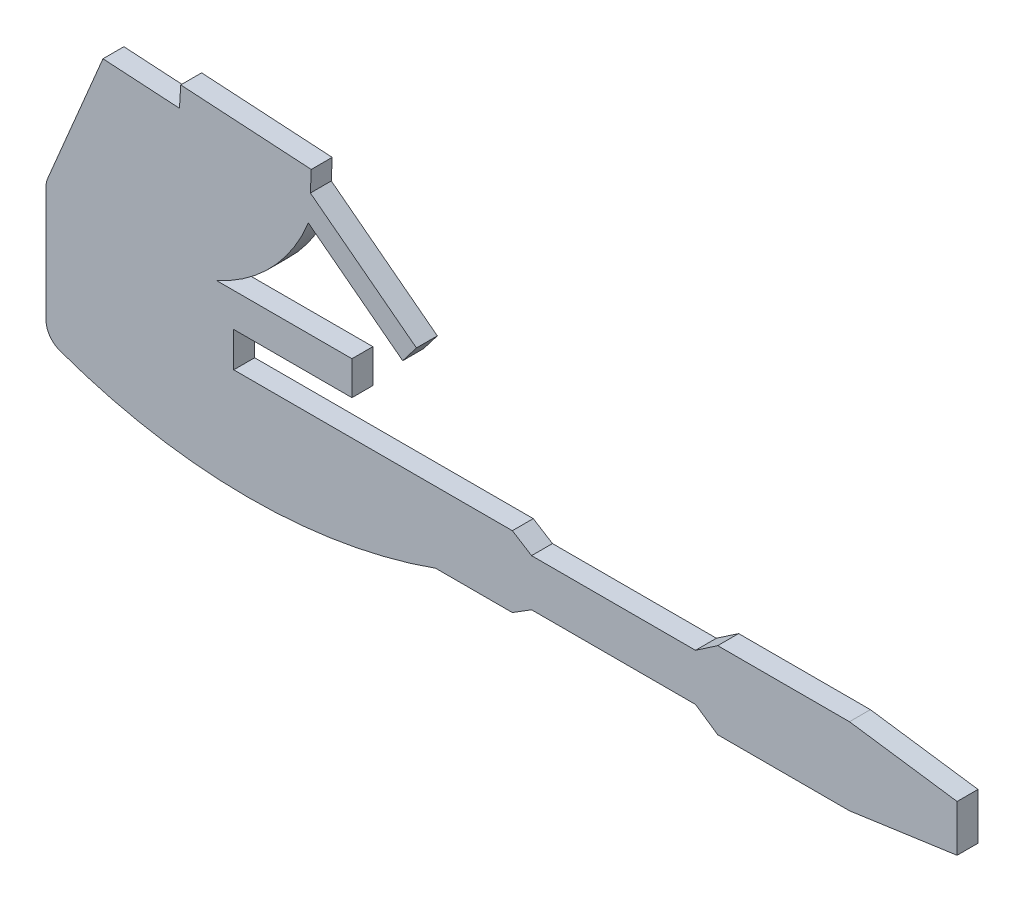
SolidWorks part; units mm, degrees
ref_plane "Front Plane" through (0, 0, 0) normal (0, 0, 1) x (1, 0, 0)
ref_plane "Top Plane" through (0, 0, 0) normal (0, 1, 0) x (1, 0, 0)
ref_plane "Right Plane" through (0, 0, 0) normal (1, 0, 0) x (0, 0, -1)
sketch "Sketch1" plane through (0, 0, 0) normal (0, 0, 1) x (1, 0, 0)
  line L0 (-76.7542, -61.1742) -> (-76.6619, -59.653)
  line L1 (-76.6619, -59.653) -> (-67.1495, -60.2304)
  line L2 (-67.1495, -60.2304) -> (-67.2138, -61.7533)
  line L3 (-67.2138, -61.7533) -> (-59.4864, -67.6638)
  line L4 (-59.4864, -67.6638) -> (-60.4861, -68.9708)
  line L5 (-60.4861, -68.9708) -> (-67.3609, -63.7124)
  line L6 (-74.0519, -70.6934) -> (-64.1851, -70.6934)
  line L7 (-64.1851, -70.6934) -> (-64.1851, -73.153)
  line L8 (-64.1851, -73.153) -> (-72.7983, -73.153)
  line L9 (-72.7983, -73.153) -> (-72.7983, -75.7018)
  line L10 (-72.7983, -75.7018) -> (-52.4958, -75.7018)
  line L11 (-52.4958, -75.7018) -> (-51.0967, -76.5771)
  line L12 (-51.0967, -76.5771) -> (-39.1499, -76.5771)
  line L13 (-27.9317, -81.0972) -> (-20.0893, -79.9849)
  line L14 (-37.5323, -81.0972) -> (-27.9317, -81.0972)
  line L15 (-39.1499, -76.5771) -> (-37.5323, -75.4744)
  line L16 (-37.5323, -75.4744) -> (-27.9317, -75.4744)
  line L17 (-27.9317, -75.4744) -> (-20.0893, -76.5867)
  line L18 (-20.0893, -76.5867) -> (-20.0893, -79.9849)
  line L19 (-36.412, -78.2858) -> (9.6345, -78.2858) construction
  line L20 (-39.1499, -79.9945) -> (-37.5323, -81.0972)
  line L21 (-51.0967, -79.9945) -> (-39.1499, -79.9945)
  line L22 (-52.4958, -80.8698) -> (-51.0967, -79.9945)
  line L23 (-58.0841, -80.8698) -> (-52.4958, -80.8698)
  line L24 (-76.7542, -61.1742) -> (-82.3278, -60.8359)
  line L25 (-82.3278, -60.8359) -> (-86.3595, -70.4097)
  line L26 (-86.4789, -71.0012) -> (-86.4789, -79.3944)
  arc A0 (-67.3609, -63.7124) -> (-74.0519, -70.6934) centre (-79.3988, -58.8716) cw
  arc A1 (-58.0841, -80.8698) -> (-85.471, -80.8283) centre (-71.7198, -42.6211) cw
  arc A2 (-86.3595, -70.4097) -> (-86.4789, -71.0012) centre (-84.9549, -71.0012) ccw
  arc A3 (-85.471, -80.8283) -> (-86.4789, -79.3944) centre (-84.9549, -79.3944) cw
extrude "Boss-Extrude1" add sketch "Sketch1" along normal blind 1.524
